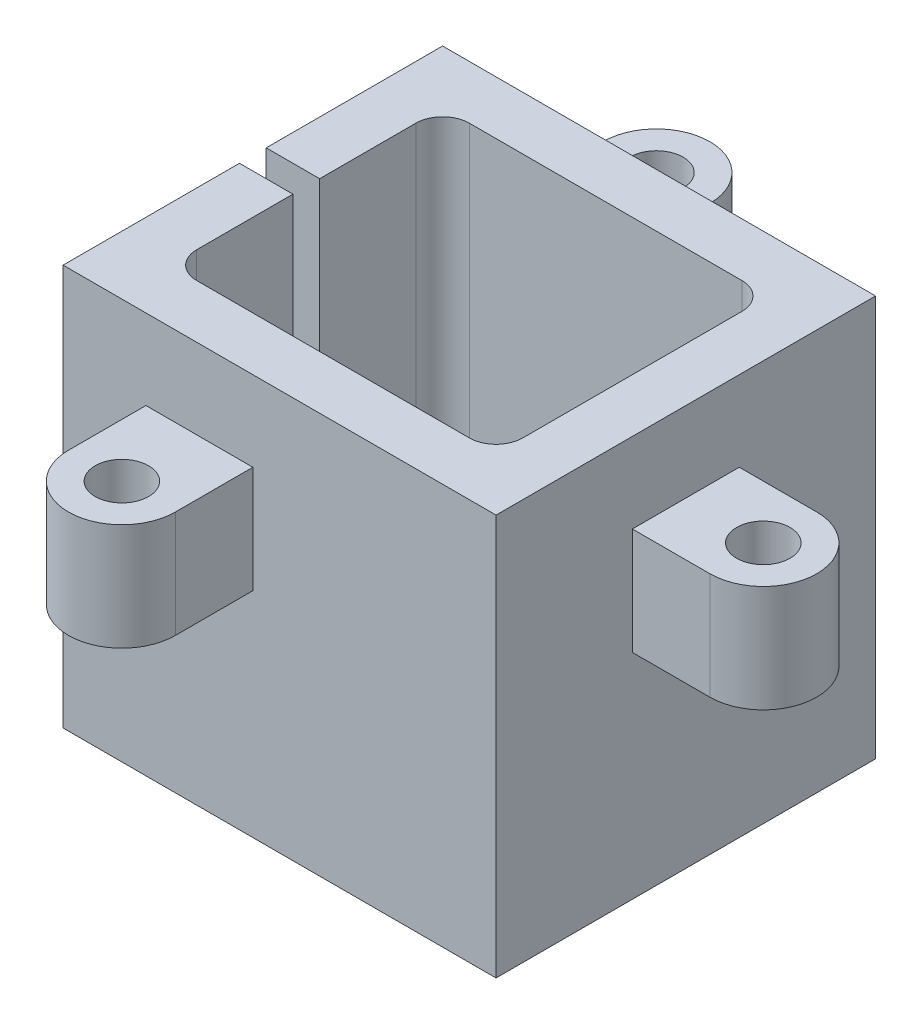
SolidWorks part; units mm, degrees
ref_plane "前视基准面" through (0, 0, 0) normal (0, 0, 1) x (1, 0, 0)
ref_plane "上视基准面" through (0, 0, 0) normal (0, 1, 0) x (1, 0, 0)
ref_plane "右视基准面" through (0, 0, 0) normal (1, 0, 0) x (0, 0, -1)
sketch "草图1" plane through (0, 0, 0) normal (0, 1, 0) x (1, 0, 0)
  line L0 (-2, -2) -> (14.2, -2)
  line L1 (0, 0) -> (12.2, 0)
  line L2 (0, 0) -> (0, 4.6)
  line L3 (0, 10.2) -> (12.2, 10.2)
  line L4 (12.2, 0) -> (12.2, 10.2)
  line L5 (14.2, -2) -> (14.2, 12.2)
  line L6 (-2, 12.2) -> (14.2, 12.2)
  line L7 (-2, -2) -> (-2, 4.6)
  line L9 (-2, 5.1) -> (0, 5.1) construction
  line L13 (-2, -2) -> (14.2, -2) construction
  line L14 (-2, 4.6) -> (0, 4.6)
  line L15 (0, 0) -> (12.2, 0) construction
  line L16 (-2, 5.6) -> (0, 5.6)
  line L17 (-2, 5.6) -> (-2, 12.2)
  line L18 (0, 5.6) -> (0, 10.2)
  line L19 (-2, -2) -> (-2, 12.2) construction
  line L21 (0, 0) -> (0, 10.2) construction
  dimension "D1" = 12.2
  dimension "D2" = 10.2
  dimension "D4" = 0.5
  dimension "D3" = 2
extrude "凸台-拉伸1" add sketch "草图1" along normal blind 15
sketch "草图2" plane through (0, 0, -5.6) normal (0, 0, 1) x (1, 0, 0)
  line L0 (-0.4676, 6.5) -> (-10.0521, 6.5) construction
  line L2 (-4, 8.5) -> (-2, 8.5)
  line L3 (-2, 8.5) -> (-2, 4.5)
  line L4 (-2, 4.5) -> (-4, 4.5)
  line L6 (-2, 15) -> (-2, 0) construction
  line L7 (-2, 15) -> (14.2, 15) construction
  arc A0 (-4, 8.5) -> (-4, 4.5) centre (-4, 6.5) ccw
  circle A1 centre (-4, 6.5) radius 1.15
  dimension "D1" = 4
  dimension "D2" = 2.3
  dimension "D3" = 2
  dimension "D4" = 8.5
extrude "凸台-拉伸2" add sketch "草图2" against normal blind 1.5
extrude "凸台-拉伸3" add sketch "草图2<2>" along normal blind 1.5 from surface starting at face at (-1, 7.5, -4.6)
sketch "草图2<2>" plane through (0, 0, -5.6) normal (0, 0, 1) x (1, 0, 0) same geometry as "草图2"
ref_plane "基准面1" through (0, 12, 0) normal (0, 1, 0) x (1, 0, 0)
sketch "草图3" plane through (0, 15, 0) normal (0, 1, 0) x (1, 0, 0)
  line L0 (-0.9, -4.9) -> (-0.9, -2)
  line L1 (-2, -2) -> (14.2, -2) construction
  line L2 (3.1, -4.9) -> (3.1, -2)
  line L3 (16.1, 7.1) -> (14.2, 7.1)
  line L4 (14.2, -2) -> (14.2, 12.2) construction
  line L5 (16.1, 3.1) -> (14.2, 3.1)
  line L6 (14.2, 7.1) -> (14.2, 3.1)
  line L7 (-0.9, -2) -> (3.1, -2)
  line L8 (-0.9, 14.6) -> (-0.9, 12.2)
  line L9 (14.2, 12.2) -> (-2, 12.2) construction
  line L10 (-0.9, 12.2) -> (3.1, 12.2)
  line L11 (3.1, 12.2) -> (3.1, 14.6)
  line L12 (6.1, 10.2) -> (6.1, 0) construction
  line L13 (0, 10.2) -> (12.2, 10.2) construction
  line L14 (12.2, 0) -> (0, 0) construction
  line L15 (12.2, 5.1) -> (3.7536, 5.1) construction
  line L16 (12.2, 10.2) -> (12.2, 0) construction
  arc A0 (-0.9, -4.9) -> (3.1, -4.9) centre (1.1, -4.9) ccw
  circle A1 centre (1.1, -4.9) radius 1.15
  arc A2 (16.1, 3.1) -> (16.1, 7.1) centre (16.1, 5.1) ccw
  circle A3 centre (16.1, 5.1) radius 1.15
  arc A4 (3.1, 14.6) -> (-0.9, 14.6) centre (1.1, 14.6) ccw
  circle A5 centre (1.1, 14.6) radius 1.15
  dimension "D1" = 4
  dimension "D2" = 2.3
  dimension "D3" = 10
  dimension "D4" = 9.5
  dimension "D5" = 5
  dimension "D7" = 5
  dimension "D8" = 10
extrude "凸台-拉伸4" [suppressed] add sketch "草图3" against normal blind 4
fillet "圆角1" radius 1 4 edges at (0, 7.5, 0) (12.2, 7.5, 0) (12.2, 7.5, -10.2) (0, 7.5, -10.2)
sketch "草图4" plane through (0, 12, 0) normal (0, 1, 0) x (1, 0, 0)
  line L0 (6.1, 12.2) -> (6.1, 5.1) construction
  line L1 (5.1, -2) -> (5.1, -4.9)
  line L2 (14.2, 5.1) -> (6.1, 5.1) construction
  line L3 (1.1, -2) -> (5.1, -2)
  line L4 (14.2, -2) -> (14.2, 12.2) construction
  line L5 (1.1, -4.9) -> (1.1, -2)
  line L6 (14.2, 12.2) -> (-2, 12.2) construction
  line L7 (1.1, 15.1) -> (1.1, 12.2)
  line L8 (1.1, 12.2) -> (5.1, 12.2)
  line L9 (5.1, 12.2) -> (5.1, 15.1)
  line L10 (17.1, 7.1) -> (14.2, 7.1)
  line L11 (14.2, 7.1) -> (14.2, 3.1)
  line L12 (14.2, 3.1) -> (17.1, 3.1)
  arc A0 (5.1, 15.1) -> (1.1, 15.1) centre (3.1, 15.1) ccw
  circle A1 centre (3.1, 15.1) radius 1
  circle A2 centre (3.1, -4.9) radius 1
  arc A3 (5.1, -4.9) -> (1.1, -4.9) centre (3.1, -4.9) cw
  arc A4 (17.1, 3.1) -> (17.1, 7.1) centre (17.1, 5.1) ccw
  circle A6 centre (17.1, 5.1) radius 1
  dimension "D1" = 10
  dimension "D2" = 4
  dimension "D3" = 2
  dimension "D4" = 11
  dimension "D5" = 3
extrude "凸台-拉伸5" add sketch "草图4" against normal blind 4
